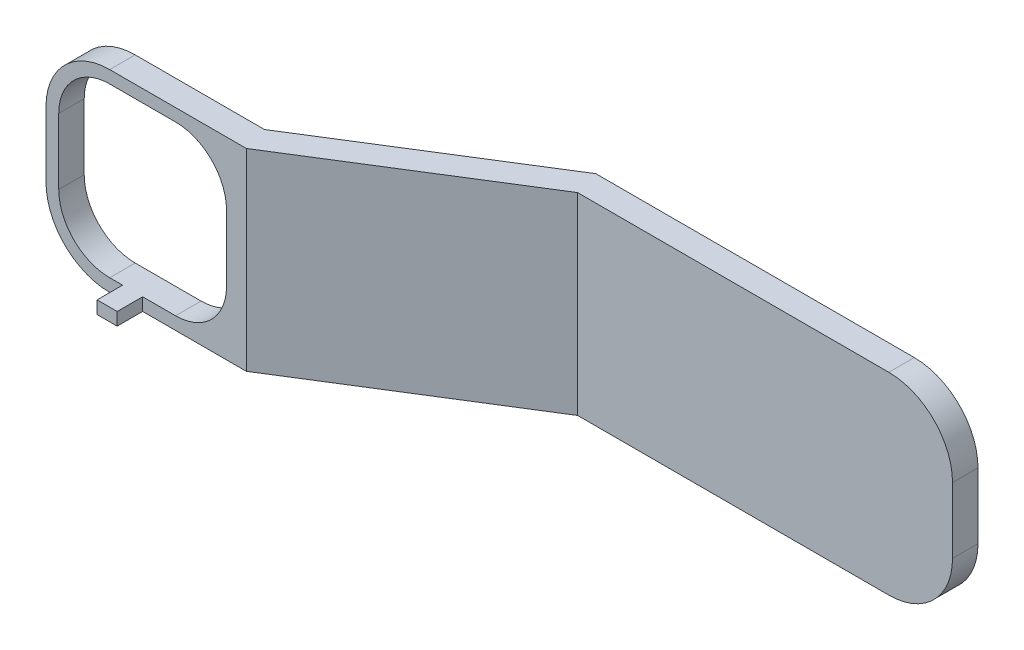
SolidWorks part; units mm, degrees
ref_plane "Front Plane" through (0, 0, 0) normal (0, 0, 1) x (1, 0, 0)
ref_plane "Top Plane" through (0, 0, 0) normal (0, 1, 0) x (1, 0, 0)
ref_plane "Right Plane" through (0, 0, 0) normal (1, 0, 0) x (0, 0, -1)
sketch "Sketch2" plane through (0, 0, 0) normal (0, 1, 0) x (1, 0, 0)
  line L0 (0, 0) -> (19.24, 0)
  line L1 (19.24, 0) -> (39.56, 12.7)
  line L2 (39.56, 12.7) -> (77.66, 12.7)
  dimension "D1" = 19.24
  dimension "D2" = 20.32
  dimension "D3" = 12.7
  dimension "D4" = 38.1
extrude "Extrude-Thin1" add sketch "Sketch2" along normal mid plane 19.24 thin thin type one direction wall 2.54
sketch "Sketch3" plane through (0, 0, 2.54) normal (0, 0, 1) x (1, 0, 0)
  line L0 (0, 9.62) -> (0, -9.62) construction
  line L1 (6.35, 8.3754) -> (12.9154, 8.3754)
  line L2 (1.27, 3.2954) -> (1.27, -3.27)
  line L3 (6.35, -8.35) -> (12.9154, -8.35)
  line L4 (17.9954, 3.2954) -> (17.9954, -3.27)
  line L6 (0, -9.62) -> (19.9685, -9.62) construction
  arc A0 (12.9154, -8.35) -> (17.9954, -3.27) centre (12.9154, -3.27) ccw
  arc A1 (1.27, -3.27) -> (6.35, -8.35) centre (6.35, -3.27) ccw
  arc A2 (12.9154, 8.3754) -> (17.9954, 3.2954) centre (12.9154, 3.2954) cw
  arc A3 (6.35, 8.3754) -> (1.27, 3.2954) centre (6.35, 3.2954) ccw
  point P8 (1.27, -8.35)
  point P11 (17.9954, 8.3754)
  point P14 (1.27, 8.3754)
  point P15 (1.27, 0.0127)
  dimension "D3" = 5.08
  dimension "D1" = 16.7254
  dimension "D2" = 16.7254
  dimension "D4" = 1.27
  dimension "D5" = 1.27
extrude "Cut-Extrude1" cut sketch "Sketch3" against normal through all
fillet "Fillet1" radius 6.35 4 edges at (77.66, -9.62, -11.43) (77.66, 9.62, -11.43) (0, -9.62, 1.27) (0, 9.62, 1.27)
sketch "Sketch4" plane through (0, 0, 2.54) normal (0, 0, 1) x (1, 0, 0)
  line L0 (6.35, -8.35) -> (12.9154, -8.35) construction
  line L1 (9.6327, -8.35) -> (7.6327, -8.35)
  line L2 (9.6327, -8.35) -> (9.6327, -9.62)
  line L3 (9.6327, -9.62) -> (7.6327, -9.62)
  line L4 (7.6327, -8.35) -> (7.6327, -9.62)
  line L5 (6.35, -9.62) -> (19.9685, -9.62) construction
  dimension "D1" = 2
extrude "Boss-Extrude1" add sketch "Sketch4" along normal blind 2.54
